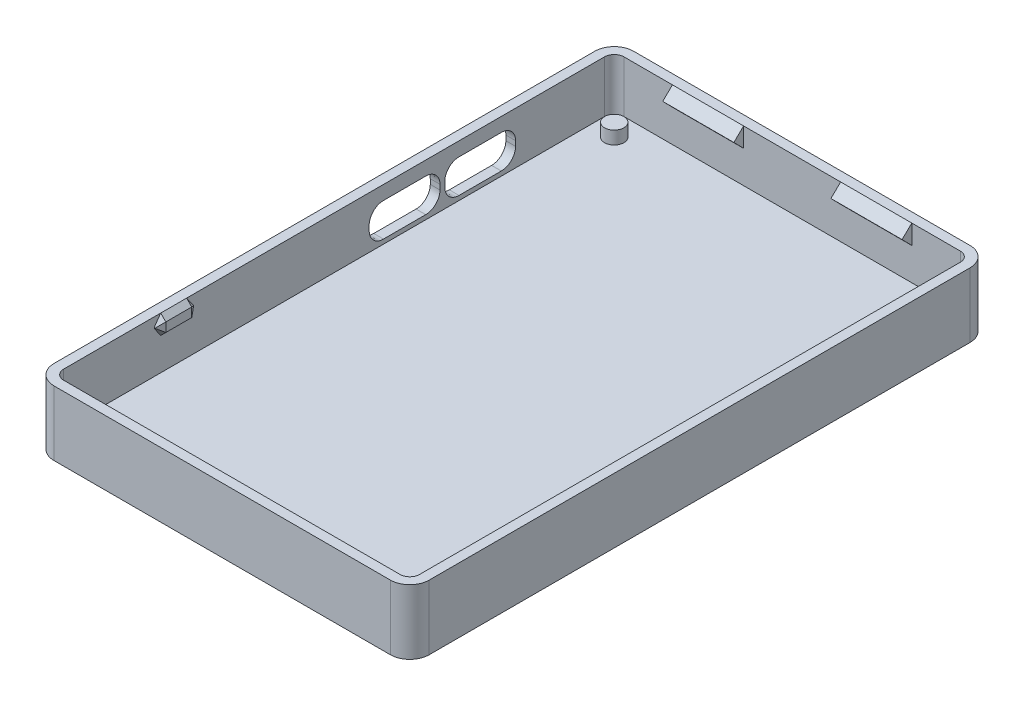
SolidWorks part; units mm, degrees
ref_plane "前视基准面" through (0, 0, 0) normal (0, 0, 1) x (1, 0, 0)
ref_plane "上视基准面" through (0, 0, 0) normal (0, 1, 0) x (1, 0, 0)
ref_plane "右视基准面" through (0, 0, 0) normal (1, 0, 0) x (0, 0, -1)
other "Configuration Table"
sketch "草图1" plane through (0, 0, 0) normal (0, 1, 0) x (1, 0, 0)
  line L1 (3, 0) -> (55, 0)
  line L2 (0, 3) -> (0, 86.6)
  line L3 (3, 89.6) -> (55, 89.6)
  line L4 (58, 3) -> (58, 86.6)
  arc A0 (58, 86.6) -> (55, 89.6) centre (55, 86.6) ccw
  arc A1 (55, 0) -> (58, 3) centre (55, 3) ccw
  arc A2 (3, 0) -> (0, 3) centre (3, 3) cw
  arc A3 (0, 86.6) -> (3, 89.6) centre (3, 86.6) cw
  point P7 (58, 89.6)
  point P10 (58, 0)
  point P13 (0, 0)
  point P16 (0, 89.6)
  dimension "D3" = 3
  dimension "D1" = 89.6
  dimension "D2" = 58
extrude "凸台-拉伸1" add sketch "草图1" along normal blind 2
sketch "草图3" plane through (0, 2, 0) normal (0, 1, 0) x (1, 0, 0)
  line L0 (0, 86.6) -> (0, 3) construction
  line L1 (3, 0) -> (55, 0) construction
  line L2 (58, 3) -> (58, 86.6) construction
  line L3 (55, 89.6) -> (3, 89.6) construction
  line L4 (0, 86.6) -> (0, 3)
  line L5 (3, 0) -> (55, 0)
  line L6 (58, 3) -> (58, 86.6)
  line L7 (55, 89.6) -> (3, 89.6)
  line L8 (1.5, 86.6) -> (1.5, 3)
  line L9 (3, 1.5) -> (55, 1.5)
  line L10 (56.5, 3) -> (56.5, 86.6)
  line L11 (55, 88.1) -> (3, 88.1)
  arc A0 (0, 3) -> (3, 0) centre (3, 3) ccw construction
  arc A1 (55, 0) -> (58, 3) centre (55, 3) ccw construction
  arc A2 (58, 86.6) -> (55, 89.6) centre (55, 86.6) ccw construction
  arc A3 (3, 89.6) -> (0, 86.6) centre (3, 86.6) ccw construction
  arc A4 (0, 3) -> (3, 0) centre (3, 3) ccw
  arc A5 (55, 0) -> (58, 3) centre (55, 3) ccw
  arc A6 (58, 86.6) -> (55, 89.6) centre (55, 86.6) ccw
  arc A7 (3, 89.6) -> (0, 86.6) centre (3, 86.6) ccw
  arc A8 (1.5, 3) -> (3, 1.5) centre (3, 3) ccw
  arc A9 (55, 1.5) -> (56.5, 3) centre (55, 3) ccw
  arc A10 (56.5, 86.6) -> (55, 88.1) centre (55, 86.6) ccw
  arc A11 (3, 88.1) -> (1.5, 86.6) centre (3, 86.6) ccw
  dimension "D1" = 1.5
extrude "凸台-拉伸2" add sketch "草图3" along normal blind 11
sketch "草图5" plane through (0, 2, 0) normal (0, 1, 0) x (1, 0, 0)
  line L0 (55, 88.1) -> (3, 88.1) construction
  line L1 (1.5, 86.6) -> (1.5, 3) construction
  line L2 (29, 89.6) -> (29, 0) construction
  line L3 (55, 89.6) -> (3, 89.6) construction
  line L4 (3, 0) -> (55, 0) construction
  line L5 (0, 44.8) -> (58, 44.8) construction
  line L6 (0, 86.6) -> (0, 3) construction
  line L7 (58, 3) -> (58, 86.6) construction
  circle A0 centre (5, 84.6) radius 1.5
  circle A1 centre (53, 84.6) radius 1.5
  circle A2 centre (53, 5) radius 1.5
  circle A3 centre (5, 5) radius 1.5
  dimension "D3" = 3
  dimension "D1" = 3.5
  dimension "D2" = 3.5
extrude "凸台-拉伸3" add sketch "草图5" along normal blind 2
sketch "草图7" plane through (0, 13, 0) normal (0, 1, 0) x (1, 0, 0)
  line L0 (3, 1.5) -> (55, 1.5) construction
  line L1 (1.5, 86.6) -> (1.5, 3) construction
  line L2 (55, 88.1) -> (3, 88.1) construction
  line L3 (56.5, 3) -> (56.5, 86.6) construction
  line L4 (0, 86.6) -> (0, 3)
  line L5 (3, 0) -> (55, 0)
  line L6 (58, 3) -> (58, 86.6)
  line L7 (55, 89.6) -> (3, 89.6)
  line L8 (0, 86.6) -> (0, 3)
  line L9 (3, 0) -> (55, 0)
  line L10 (58, 3) -> (58, 86.6)
  line L11 (55, 89.6) -> (3, 89.6)
  line L12 (3, 1.5) -> (55, 1.5)
  line L13 (1.5, 86.6) -> (1.5, 3)
  line L14 (55, 88.1) -> (3, 88.1)
  line L15 (56.5, 3) -> (56.5, 86.6)
  arc A0 (55, 1.5) -> (56.5, 3) centre (55, 3) ccw construction
  arc A1 (1.5, 3) -> (3, 1.5) centre (3, 3) ccw construction
  arc A2 (3, 88.1) -> (1.5, 86.6) centre (3, 86.6) ccw construction
  arc A3 (56.5, 86.6) -> (55, 88.1) centre (55, 86.6) ccw construction
  arc A4 (3, 89.6) -> (0, 86.6) centre (3, 86.6) ccw
  arc A5 (0, 3) -> (3, 0) centre (3, 3) ccw
  arc A6 (55, 0) -> (58, 3) centre (55, 3) ccw
  arc A7 (58, 86.6) -> (55, 89.6) centre (55, 86.6) ccw
  arc A8 (3, 89.6) -> (0, 86.6) centre (3, 86.6) ccw
  arc A9 (0, 3) -> (3, 0) centre (3, 3) ccw
  arc A10 (55, 0) -> (58, 3) centre (55, 3) ccw
  arc A11 (58, 86.6) -> (55, 89.6) centre (55, 86.6) ccw
  arc A12 (55, 1.5) -> (56.5, 3) centre (55, 3) ccw
  arc A13 (1.5, 3) -> (3, 1.5) centre (3, 3) ccw
  arc A14 (3, 88.1) -> (1.5, 86.6) centre (3, 86.6) ccw
  arc A15 (56.5, 86.6) -> (55, 88.1) centre (55, 86.6) ccw
  dimension "D1" = 0
extrude "切除-拉伸2" cut sketch "草图7" against normal blind 3
sketch3d "3D草图3"
  line L0 (55, 2, -88.1) -> (3, 2, -88.1) construction
  line L1 (56.5, 2, -3) -> (56.5, 2, -86.6) construction
  line L4 (1.5, 2, -86.6) -> (1.5, 2, -3) construction
  point P0 (40, 2, -88.1)
  dimension "D1" = 16.5
  dimension "D2" = 55
sketch "草图8" plane through (0, 0, -88.1) normal (0, 0, 1) x (1, 0, 0)
  line L0 (29, 2) -> (29, 10) construction
  line L1 (10.5, 10) -> (21.5, 10)
  line L2 (10.5, 10) -> (10.5, 7)
  line L3 (10.5, 7) -> (21.5, 7)
  line L4 (55, 2) -> (55, 10)
  line L5 (55, 10) -> (3, 10)
  line L6 (3, 10) -> (3, 2)
  line L7 (3, 2) -> (55, 2)
  line L8 (55, 2) -> (55, 10)
  line L9 (55, 10) -> (3, 10)
  line L10 (3, 10) -> (3, 2)
  line L11 (3, 2) -> (55, 2)
  line L12 (21.5, 10) -> (21.5, 7)
  line L13 (47.5, 7) -> (36.5, 7)
  line L14 (36.5, 10) -> (36.5, 7)
  line L15 (47.5, 10) -> (36.5, 10)
  line L16 (47.5, 10) -> (47.5, 7)
  line M10 (55, 10) -> (3, 10)
  dimension "D2" = 11
  dimension "D3" = 3
  dimension "D4" = 7.5
  dimension "D1" = 0
extrude "凸台-拉伸4" add sketch "草图8" along normal blind 1.5 contours L12 L2 L3 M10 | L16 L9 L14 L13 region at (16, 8.5, -88.1) region at (42, 8.5, -88.1)
sketch "草图10" plane through (10.5, 0, 0) normal (-1, 0, 0) x (0, 0, 1)
  line L0 (-88.1, 8.5343) -> (-86.6, 8.5343) construction
  line L1 (-88.1, 10) -> (-86.6, 8.5343)
  line L2 (-86.6, 8.5343) -> (-88.1, 7)
  line L4 (-88.1, 10) -> (-88.1, 7)
  line L5 (-88.1, 7) -> (-86.6, 7)
  line L6 (-86.6, 7) -> (-86.6, 10)
  line L7 (-86.6, 10) -> (-88.1, 10)
  line L8 (-88.1, 10) -> (-88.1, 7)
  line L9 (-88.1, 7) -> (-86.6, 7)
  line L10 (-86.6, 7) -> (-86.6, 10)
  line L11 (-86.6, 10) -> (-88.1, 10)
  line M6 (-88.1, 7) -> (-86.6, 7)
  line M7 (-86.6, 7) -> (-86.6, 10)
  line M8 (-86.6, 10) -> (-88.1, 10)
  dimension "D1" = 0
extrude "切除-拉伸3" cut sketch "草图10" against normal blind 40 contours L1 M8 M7 | L2 M7 M6 region at (10.5, 9.5114, -87.1) region at (10.5, 7.5114, -87.1)
sketch "草图11" plane through (1.5, 0, 0) normal (1, 0, 0) x (0, 0, -1)
  line L1 (17, 10) -> (23, 10)
  line L2 (17, 10) -> (17, 7)
  line L3 (17, 7) -> (23, 7)
  line L4 (86.6, 2) -> (86.6, 10)
  line L5 (86.6, 10) -> (3, 10)
  line L6 (3, 10) -> (3, 2)
  line L7 (3, 2) -> (86.6, 2)
  line L8 (86.6, 2) -> (86.6, 10)
  line L9 (86.6, 10) -> (3, 10)
  line L10 (3, 10) -> (3, 2)
  line L11 (3, 2) -> (86.6, 2)
  line L12 (23, 10) -> (23, 7)
  dimension "D2" = 14
  dimension "D3" = 6
  dimension "D4" = 3
  dimension "D1" = 0
extrude "凸台-拉伸5" add sketch "草图11" along normal blind 1.5 contours L1 L12 L3 L2
sketch "草图12" plane through (0, 0, -17) normal (0, 0, 1) x (1, 0, 0)
  line L0 (3, 8.5) -> (1.5, 8.5) construction
  line L1 (3, 8.5) -> (1.5, 10)
  line L2 (1.5, 7) -> (3, 8.5)
  line L4 (1.5, 10) -> (1.5, 7)
  line L5 (1.5, 7) -> (3, 7)
  line L6 (3, 7) -> (3, 10)
  line L7 (3, 10) -> (1.5, 10)
  line L8 (1.5, 10) -> (1.5, 7)
  line L9 (1.5, 7) -> (3, 7)
  line L10 (3, 7) -> (3, 10)
  line L11 (3, 10) -> (1.5, 10)
  line M6 (1.5, 7) -> (3, 7)
  line M7 (3, 7) -> (3, 10)
  line M8 (3, 10) -> (1.5, 10)
  dimension "D1" = 0
extrude "切除-拉伸4" cut sketch "草图12" against normal blind 7 contours L1 M7 M8 | L2 M6 M7 region at (2.5, 7.5, -17) region at (2.5, 9.5, -17)
sketch "草图13" plane through (56.5, 0, 0) normal (-1, 0, 0) x (0, 0, 1)
  line L1 (-23, 10) -> (-17, 10)
  line L2 (-23, 10) -> (-23, 7)
  line L3 (-23, 7) -> (-17, 7)
  line L4 (-3, 2) -> (-3, 10)
  line L5 (-3, 10) -> (-86.6, 10)
  line L6 (-86.6, 10) -> (-86.6, 2)
  line L7 (-86.6, 2) -> (-3, 2)
  line L8 (-3, 2) -> (-3, 10)
  line L9 (-3, 10) -> (-86.6, 10)
  line L10 (-86.6, 10) -> (-86.6, 2)
  line L11 (-86.6, 2) -> (-3, 2)
  line L12 (-17, 10) -> (-17, 7)
  line M6 (-3, 10) -> (-86.6, 10)
  dimension "D2" = 14
  dimension "D3" = 6
  dimension "D4" = 3
  dimension "D1" = 0
extrude "凸台-拉伸6" add sketch "草图13" along normal blind 1.5 contours L12 L2 L3 M6 region at (56.5, 8.5, -20)
sketch "草图15" plane through (0, 0, -23) normal (0, 0, -1) x (-1, 0, 0)
  line L0 (-56.5, 10) -> (-55, 8.5)
  line L1 (-55, 8.5) -> (-56.5, 7)
  line L4 (-56.5, 10) -> (-56.5, 7)
  line L5 (-56.5, 7) -> (-55, 7)
  line L6 (-55, 7) -> (-55, 10)
  line L7 (-55, 10) -> (-56.5, 10)
  line L8 (-56.5, 10) -> (-56.5, 7)
  line L9 (-56.5, 7) -> (-55, 7)
  line L10 (-55, 7) -> (-55, 10)
  line L11 (-55, 10) -> (-56.5, 10)
  line M6 (-56.5, 7) -> (-55, 7)
  line M7 (-55, 7) -> (-55, 10)
  line M8 (-55, 10) -> (-56.5, 10)
  dimension "D1" = 0
extrude "切除-拉伸5" cut sketch "草图15" against normal blind 7 contours L0 M8 M7 | L1 M7 M6 region at (55.5, 9.5, -23) region at (55.5, 7.5, -23)
chamfer "倒角1" distance 1 angle 45 5 edges at (2.25, 7.75, -17) (2.25, 7.75, -23) (2.25, 9.25, -23) (3, 8.5, -20) (2.25, 9.25, -17)
chamfer "倒角2" distance 1 angle 45 5 edges at (55.75, 7.75, -23) (55.75, 7.75, -17) (55.75, 9.25, -17) (55.75, 9.25, -23) (55, 8.5, -20)
extrude "切除-拉伸6" cut sketch "草图16" against normal blind 2 contours S23 L27 S22 L26 S21 L25 S20 L24 L6 S7 L7 S5 L4 S4 L5 S6 | S7 L6 S6 L5 S4 L4 S5 L7 | S31 L31 S30 L30 S29 L29 S28 L28 L23 S15 L20 S12 L21 S13 L22 S14 | S15 L23 S14 L22 S13 L21 S12 L20 region at (0, 5.27, -67.3785) region at (0, 5.27, -55.6945) region at (0, 7.7291, -67.3785) region at (0, 7.7291, -55.6945)
sketch "草图16" plane through (0, 2, -82.9995) normal (-1, 0, 0) x (0, 1, 0)
  line L4 (3.65, -20.091) -> (2.89, -20.091)
  line L5 (1.69, -18.891) -> (1.69, -12.351)
  line L6 (2.89, -11.151) -> (3.65, -11.151)
  line L7 (4.85, -12.351) -> (4.85, -18.891)
  line L16 (-2, 3.6005) -> (-2, -79.9995)
  line L17 (-2, -79.9995) -> (8, -79.9995)
  line L19 (8, 3.6005) -> (-2, 3.6005)
  line L20 (4.85, -24.0351) -> (4.85, -30.5751)
  line L21 (3.65, -31.7751) -> (2.89, -31.7751)
  line L22 (1.69, -30.5751) -> (1.69, -24.0351)
  line L23 (2.89, -22.8351) -> (3.65, -22.8351)
  line L24 (5.85, -12.351) -> (5.85, -18.891)
  line L25 (3.65, -21.091) -> (2.89, -21.091)
  line L26 (0.69, -18.891) -> (0.69, -12.351)
  line L27 (2.89, -10.151) -> (3.65, -10.151)
  line L28 (5.85, -24.0351) -> (5.85, -30.5751)
  line L29 (3.65, -32.7751) -> (2.89, -32.7751)
  line L30 (0.69, -30.5751) -> (0.69, -24.0351)
  line L31 (2.89, -21.8351) -> (3.65, -21.8351)
  line L36 (8, -79.9995) -> (8, 3.6005)
  spline S4 degree 3 poles (2.89, -20.091) (2.1871, -20.091) (1.69, -19.594) (1.69, -18.891) knots 0 0 0 0 1 1 1 1 weights 1 0.804738 0.804738 1
  spline S5 degree 3 poles (4.85, -18.891) (4.85, -19.594) (4.353, -20.091) (3.65, -20.091) knots 0 0 0 0 1 1 1 1 weights 1 0.804738 0.804738 1
  spline S6 degree 3 poles (1.69, -12.351) (1.69, -11.6481) (2.1871, -11.151) (2.89, -11.151) knots 0 0 0 0 1 1 1 1 weights 1 0.804738 0.804738 1
  spline S7 degree 3 poles (3.65, -11.151) (4.353, -11.151) (4.85, -11.6481) (4.85, -12.351) knots 0 0 0 0 1 1 1 1 weights 1 0.804738 0.804738 1
  spline S12 degree 3 poles (4.85, -30.5751) (4.85, -31.278) (4.353, -31.7751) (3.65, -31.7751) knots 0 0 0 0 1 1 1 1 weights 1 0.804738 0.804738 1
  spline S13 degree 3 poles (2.89, -31.7751) (2.1871, -31.7751) (1.69, -31.278) (1.69, -30.5751) knots 0 0 0 0 1 1 1 1 weights 1 0.804738 0.804738 1
  spline S14 degree 3 poles (1.69, -24.0351) (1.69, -23.3321) (2.1871, -22.8351) (2.89, -22.8351) knots 0 0 0 0 1 1 1 1 weights 1 0.804738 0.804738 1
  spline S15 degree 3 poles (3.65, -22.8351) (4.353, -22.8351) (4.85, -23.3321) (4.85, -24.0351) knots 0 0 0 0 1 1 1 1 weights 1 0.804738 0.804738 1
  spline S20 degree 3 poles (5.85, -18.891) (5.85, -19.1658) (5.7555, -19.7032) (5.2541, -20.4951) (4.4622, -20.9965) (3.9248, -21.091) (3.65, -21.091) knots 0 0 0 0 0.25 0.5 0.75 1 1 1 1
  spline S21 degree 3 poles (2.89, -21.091) (2.6152, -21.091) (2.0779, -20.9965) (1.286, -20.4951) (0.7845, -19.7032) (0.69, -19.1658) (0.69, -18.891) knots 0 0 0 0 0.25 0.5 0.75 1 1 1 1
  spline S22 degree 3 poles (0.69, -12.351) (0.69, -12.0762) (0.7845, -11.5389) (1.286, -10.747) (2.0779, -10.2456) (2.6152, -10.151) (2.89, -10.151) knots 0 0 0 0 0.25 0.5 0.75 1 1 1 1
  spline S23 degree 3 poles (3.65, -10.151) (3.9248, -10.151) (4.4622, -10.2456) (5.2541, -10.747) (5.7555, -11.5389) (5.85, -12.0762) (5.85, -12.351) knots 0 0 0 0 0.25 0.5 0.75 1 1 1 1
  spline S28 degree 3 poles (5.85, -30.5751) (5.85, -30.8499) (5.7555, -31.3872) (5.2541, -32.1791) (4.4622, -32.6805) (3.9248, -32.7751) (3.65, -32.7751) knots 0 0 0 0 0.25 0.5 0.75 1 1 1 1
  spline S29 degree 3 poles (2.89, -32.7751) (2.6152, -32.7751) (2.0779, -32.6805) (1.286, -32.1791) (0.7845, -31.3872) (0.69, -30.8499) (0.69, -30.5751) knots 0 0 0 0 0.25 0.5 0.75 1 1 1 1
  spline S30 degree 3 poles (0.69, -24.0351) (0.69, -23.7603) (0.7845, -23.2229) (1.286, -22.431) (2.0779, -21.9296) (2.6152, -21.8351) (2.89, -21.8351) knots 0 0 0 0 0.25 0.5 0.75 1 1 1 1
  spline S31 degree 3 poles (3.65, -21.8351) (3.9248, -21.8351) (4.4622, -21.9296) (5.2541, -22.431) (5.7555, -23.2229) (5.85, -23.7603) (5.85, -24.0351) knots 0 0 0 0 0.25 0.5 0.75 1 1 1 1
